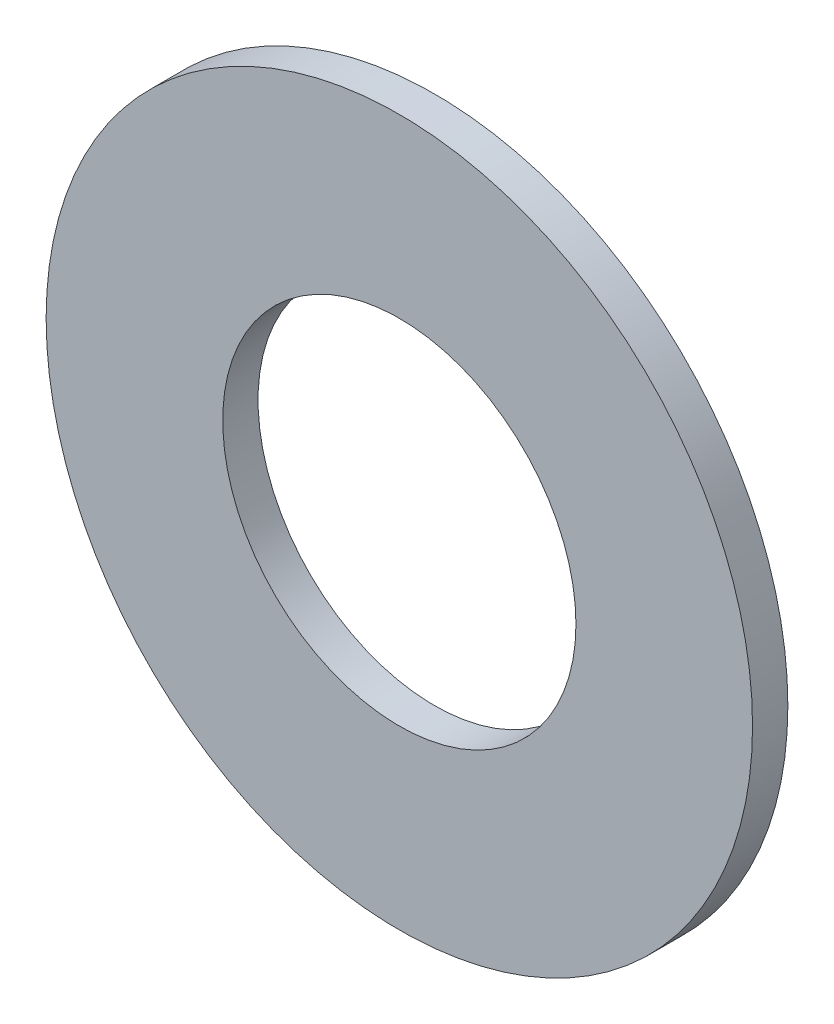
SolidWorks part; units mm, degrees
material "Сталь ШХ15 ГОСТ 801-78"
ref_plane "Plane1" through (0, 0, 0) normal (0, 0, 1) x (1, 0, 0)
ref_plane "Plane2" through (0, 0, 0) normal (0, 1, 0) x (1, 0, 0)
ref_plane "Plane3" through (0, 0, 0) normal (1, 0, 0) x (0, 0, -1)
sketch "Эскиз1" plane through (0, 0, 0) normal (0, 0, 1) x (1, 0, 0)
  circle A0 centre (0, 0) radius 10
  circle A1 centre (0, 0) radius 5
  dimension "D1" = 20
  dimension "D2" = 10
extrude "Бобышка-Вытянуть1" add sketch "Эскиз1" along normal blind 1 contours A1 | A0 region at (0, 0, 0)
